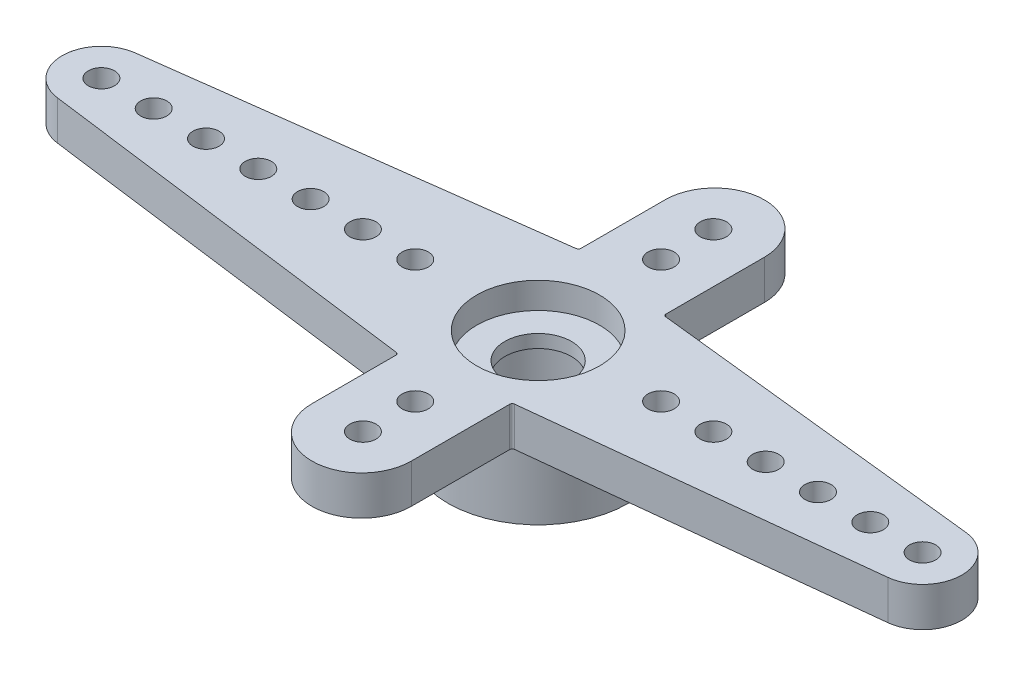
SolidWorks part; units mm, degrees
ref_plane "Ön Düzlem" through (0, 0, 0) normal (0, 0, 1) x (1, 0, 0)
ref_plane "Üst Düzlem" through (0, 0, 0) normal (0, 1, 0) x (1, 0, 0)
ref_plane "Sağ Düzlem" through (0, 0, 0) normal (1, 0, 0) x (0, 0, -1)
sketch "Çizim1" plane through (0, 0, 0) normal (0, 1, 0) x (1, 0, 0)
  line L0 (0, 11.8418) -> (0, -11.8418) construction
  line L1 (-16.7, 0) -> (14.7, 0) construction
  line L2 (-16.7, 0) -> (-14.7, 0) construction
  line L3 (14.7, 0) -> (12.7, 0) construction
  line L4 (-1.9, 6.75) -> (-1.9, 3.45)
  line L5 (1.9, -6.75) -> (1.9, -2.9)
  line L6 (-16.8947, 1.4873) -> (-1.9, 3.45)
  line L7 (-16.8947, -1.4873) -> (-1.9, -3.45)
  line L8 (14.8621, 1.4912) -> (1.9, 2.9)
  line L9 (14.8621, -1.4912) -> (1.9, -2.9)
  line L10 (1.9, 2.9) -> (1.9, 6.75)
  line L11 (-1.9, -3.45) -> (-1.9, -6.75)
  circle A0 centre (0, 0) radius 1.275
  circle A1 centre (0, 0) radius 2.35
  circle A2 centre (-16.7, 0) radius 0.5
  arc A3 (-16.8947, 1.4873) -> (-16.8947, -1.4873) centre (-16.7, 0) ccw
  circle A4 centre (-14.7, 0) radius 0.5
  circle A5 centre (-12.7, 0) radius 0.5
  circle A6 centre (-10.7, 0) radius 0.5
  circle A7 centre (-8.7, 0) radius 0.5
  circle A8 centre (-6.7, 0) radius 0.5
  circle A9 centre (-4.7, 0) radius 0.5
  circle A10 centre (14.7, 0) radius 0.5
  arc A11 (14.8621, -1.4912) -> (14.8621, 1.4912) centre (14.7, 0) ccw
  circle A12 centre (12.7, 0) radius 0.5
  circle A13 centre (10.7, 0) radius 0.5
  circle A14 centre (8.7, 0) radius 0.5
  circle A15 centre (6.7, 0) radius 0.5
  circle A16 centre (4.7, 0) radius 0.5
  circle A17 centre (0, 6.7) radius 0.5
  circle A18 centre (0, 4.7) radius 0.5
  circle A19 centre (0, -6.7) radius 0.5
  circle A20 centre (0, -4.7) radius 0.5
  arc A22 (-1.9, -6.75) -> (1.9, -6.75) centre (0, -6.75) ccw
  arc A23 (1.9, 6.75) -> (-1.9, 6.75) centre (0, 6.75) ccw
  point P5 (13.2, 0)
  point P6 (0, 0)
  point P10 (-17.2, 0)
  point P11 (-16.2, 0)
  point P14 (-2.35, 0)
  point P15 (2.35, 0)
  point P16 (16.2, 0)
  point P32 (14.2, 0)
  point P45 (4.2, 0)
  point P55 (0, 2.35)
  point P57 (-18.2, 0)
  point P62 (0, 8.65)
  point P63 (0, 7.2)
  point P64 (0, -7.2)
  point P65 (0, -8.65)
  point P66 (0, -2.35)
  dimension "D1" = 2.55
  dimension "D2" = 4.7
  dimension "D3" = 1
  dimension "D4" = 13.85
  dimension "D5" = 3
  dimension "D8" = 1
  dimension "D9" = 3
  dimension "D13" = 1
  dimension "D16" = 3.8
  dimension "D7" = 2
  dimension "D11" = 2
  dimension "D12" = 11.85
  dimension "D14" = 2
  dimension "D15" = 2
  dimension "D17" = 1.45
  dimension "D18" = 1.45
  dimension "D19" = 17.3
  dimension "D20" = 6.3
  dimension "D21" = 6.9
  dimension "D22" = 5.8
  dimension "D23" = 34.4
  dimension "D6" = 7
  dimension "D10" = 6
extrude "Yükseklik-Ekstrüzyon1" add sketch "Çizim1" along normal blind 1.5 contours L10 A23 L4 L6 A3 L7 L11 A22 L5 L9 A11 L8 A1 A2 A4 A5 A6 A7 A8 A9 A10 A12 A13 A14 A15 A16 A17 A18 A19 A20 region at (0, 0, -8.2649)
extrude "Yükseklik-Ekstrüzyon2" add sketch "Çizim1<3>" along normal blind 0.5 contours A1 A0 region at (-2.2835, 0, 0)
sketch "Çizim1<3>" plane through (0, 0, 0) normal (0, 1, 0) x (1, 0, 0) same geometry as "Çizim1"
sketch "Çizim2" plane through (0, 0, 0) normal (0, -1, 0) x (1, 0, 0)
  circle A0 centre (0, 0) radius 3.45
  circle A1 centre (0, 0) radius 2.3
  dimension "D1" = 6.9
  dimension "D2" = 1.15
extrude "Yükseklik-Ekstrüzyon3" add sketch "Çizim2" along normal blind 2.5
fillet "Radyus1" radius 0.1 4 edges at (-1.9, 0.75, -3.45) (1.9, 0.75, -2.9) (1.9, 0.75, 2.9) (-1.9, 0.75, 3.45)
